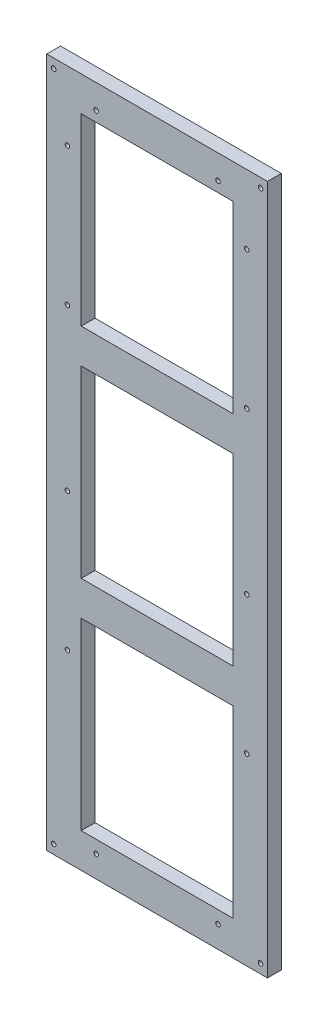
SolidWorks part; units mm, degrees
material "Alumina"
ref_plane "Front Plane" through (0, 0, 0) normal (0, 0, 1) x (1, 0, 0)
ref_plane "Top Plane" through (0, 0, 0) normal (0, 1, 0) x (1, 0, 0)
ref_plane "Right Plane" through (0, 0, 0) normal (1, 0, 0) x (0, 0, -1)
sketch "Sketch1" plane through (0, 0, 0) normal (0, 0, 1) x (1, 0, 0)
  line L0 (33, 141) -> (33, 61)
  line L9 (-48, -144) -> (48, -144)
  line L10 (-48, -144) -> (-48, 156)
  line L11 (-48, 156) -> (48, 156)
  line L12 (48, -144) -> (48, 156)
  line L14 (0, 0) -> (0, 46) construction
  line L15 (-33, -129) -> (33, -129)
  line L17 (-33, 141) -> (33, 141)
  line L19 (-33, 46) -> (-33, -34)
  line L20 (-33, -49) -> (-33, -129)
  line L21 (-33, 61) -> (33, 61)
  line L23 (-33, 46) -> (33, 46)
  line L25 (-33, -34) -> (33, -34)
  line L27 (-33, -49) -> (33, -49)
  line L33 (33, 46) -> (33, -34)
  line L34 (-33, 61) -> (-33, 141)
  line L36 (33, -49) -> (33, -129)
  dimension "D1" = 96
  dimension "D2" = 15
  dimension "D3" = 66
  dimension "D4" = 80
  dimension "D5" = 15
  dimension "D6" = 80
  dimension "D7" = 15
  dimension "D8" = 80
  dimension "D9" = 46
  dimension "D10" = 15
  dimension "D12" = 15
extrude "Boss-Extrude1" add sketch "Sketch1" along normal blind 6
sketch "Sketch3" plane through (0, 0, 6) normal (0, 0, 1) x (1, 0, 0)
  line L0 (48, 156) -> (-48, 156) construction
  line L1 (-48, 156) -> (-48, -144) construction
  line L2 (0, -3.3) -> (0, 3.3) construction
  line L3 (-48, -144) -> (48, -144) construction
  circle A0 centre (-39, 126) radius 1
  circle A26 centre (-39, -4) radius 1
  circle A29 centre (-39, 66) radius 1
  circle A33 centre (-39, -64) radius 1
  circle A41 centre (39, -64) radius 1
  circle A42 centre (39, -4) radius 1
  circle A43 centre (39, 66) radius 1
  circle A44 centre (39, 126) radius 1
  dimension "D1" = 30
  dimension "D6" = 9
  dimension "D3" = 2
  dimension "D8" = 9
  dimension "D9" = 9
  dimension "D10" = 2
  dimension "D12" = 2
  dimension "D14" = 9
  dimension "D4" = 2
  dimension "D2" = 60
  dimension "D7" = 70
  dimension "D5" = 80
extrude "Cut-Extrude6" cut sketch "Sketch3" against normal blind 10
ref_plane "Plane1" through (0, 6, 0) normal (0, 1, 0) x (1, 0, 0)
sketch "Sketch5" plane through (0, 0, 6) normal (0, 0, 1) x (1, 0, 0)
  line L0 (-26.5, 145.5) -> (26.5, 145.5) construction
  line L1 (26.5, 145.5) -> (26.5, -134.5) construction
  line L2 (26.5, -134.5) -> (-26.5, -134.5) construction
  line L3 (-26.5, -134.5) -> (-26.5, 145.5) construction
  line L4 (48, 156) -> (-48, 156) construction
  line L5 (-48, -144) -> (48, -144) construction
  line L6 (48, -144) -> (48, 156) construction
  line L7 (-48, 156) -> (-48, -144) construction
  circle A0 centre (-26.5, -134.5) radius 1
  circle A1 centre (26.5, -134.5) radius 1
  circle A2 centre (-26.5, 145.5) radius 1
  circle A3 centre (26.5, 145.5) radius 1
  dimension "D5" = 2
  dimension "D6" = 2
  dimension "D7" = 2
  dimension "D8" = 2
  dimension "D1" = 10.5
  dimension "D2" = 9.5
  dimension "D3" = 21.5
  dimension "D4" = 21.5
extrude "Cut-Extrude9" cut sketch "Sketch5" against normal blind 10
sketch "Sketch7" plane through (0, 0, 6) normal (0, 0, 1) x (1, 0, 0)
  line L0 (-45, 152) -> (45, 152) construction
  line L1 (45, 152) -> (45, -140) construction
  line L2 (45, -140) -> (-45, -140) construction
  line L3 (-45, -140) -> (-45, 152) construction
  line L4 (-48, 156) -> (-48, -144) construction
  line L5 (48, -144) -> (48, 156) construction
  line L6 (48, 156) -> (-48, 156) construction
  line L7 (-48, -144) -> (48, -144) construction
  circle A0 centre (45, -140) radius 1
  circle A1 centre (-45, -140) radius 1
  circle A2 centre (45, 152) radius 1
  circle A3 centre (-45, 152) radius 1
  dimension "D5" = 2
  dimension "D6" = 2
  dimension "D7" = 2
  dimension "D8" = 2
  dimension "D1" = 3
  dimension "D2" = 3
  dimension "D3" = 4
  dimension "D4" = 4
extrude "Cut-Extrude10" cut sketch "Sketch7" against normal blind 10
